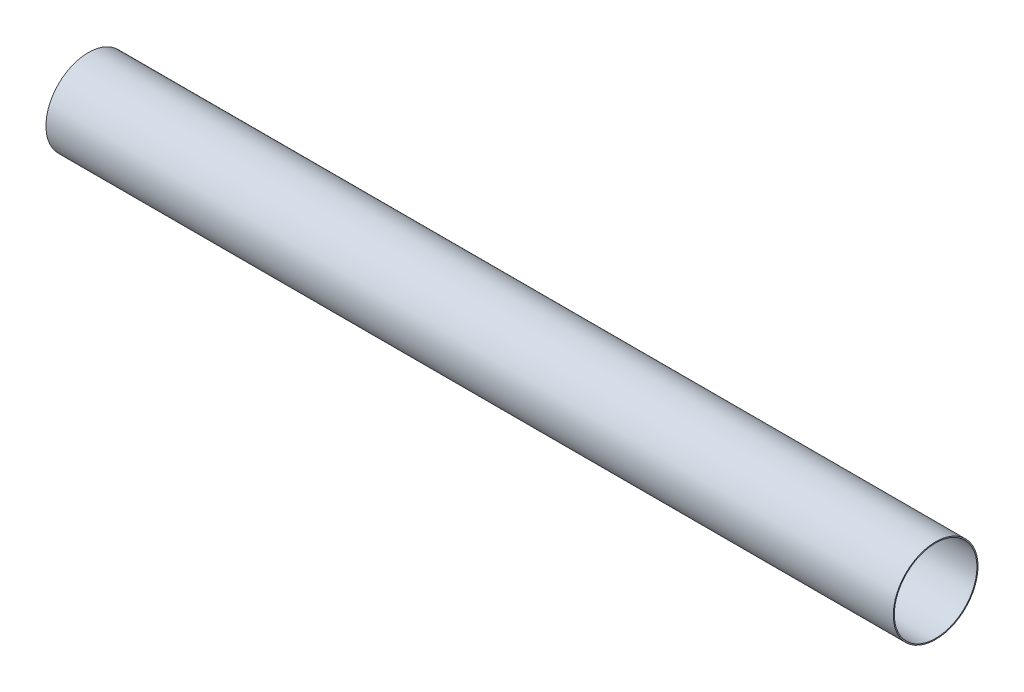
SolidWorks part; units mm, degrees
material "6061-T6 (SS)"
ref_plane "Front Plane" through (0, 0, 0) normal (0, 0, 1) x (1, 0, 0)
ref_plane "Top Plane" through (0, 0, 0) normal (0, 1, 0) x (1, 0, 0)
ref_plane "Right Plane" through (0, 0, 0) normal (1, 0, 0) x (0, 0, -1)
sketch "Sketch1" plane through (0, 0, 0) normal (1, 0, 0) x (0, 0, -1)
  circle A0 centre (0, 0) radius 152.4
  circle A1 centre (0, 0) radius 148.59
  dimension "D2" = 304.8
  dimension "D1" = 297.18
extrude "Boss-Extrude1" add sketch "Sketch1" along normal blind 3048
equation "\"P\"= 600'tank pressure in psi"
equation "\"D\"= 12in'rocket diameter, in"
equation "\"S\"= 40000'yield strength of aluminum 6061t6, psi"
equation "\"fos\"= 1.5'minimum factor of safety"
equation "\"t\"= 0.15in'new tank wall thickness, Huzel and Huang calcs"
equation "\"height\"= 120in'tank wall height, in"
equation "\"D2@Sketch1\"=\"D\""
equation "\"D1@Boss-Extrude1\"=\"height\""
